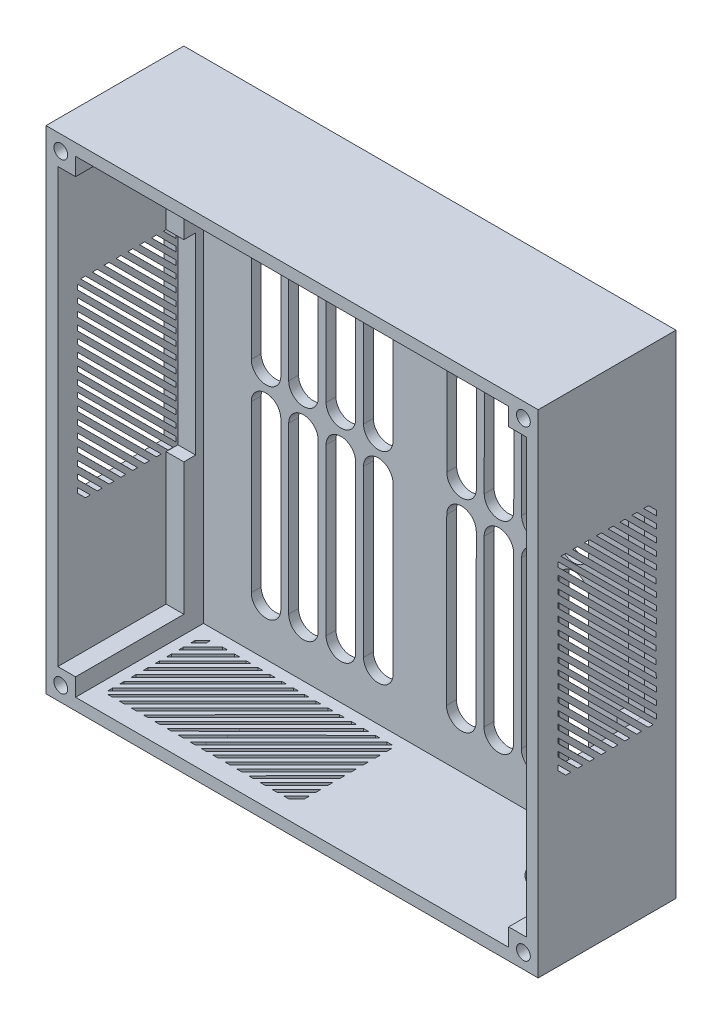
SolidWorks part; units mm, degrees
ref_plane "Plano frontal" through (0, 0, 0) normal (0, 0, 1) x (1, 0, 0)
ref_plane "Plano superior" through (0, 0, 0) normal (0, 1, 0) x (1, 0, 0)
ref_plane "Plano direito" through (0, 0, 0) normal (1, 0, 0) x (0, 0, -1)
sketch "Esboço1" plane through (0, 0, 0) normal (0, 0, 1) x (1, 0, 0)
  line L1 (-16.5696, 239.8339) -> (233.4304, 239.8339)
  line L2 (-16.5696, 239.8339) -> (-16.5696, -10.1661)
  line L3 (-16.5696, -10.1661) -> (233.4304, -10.1661)
  line L4 (233.4304, 239.8339) -> (233.4304, -10.1661)
  dimension "D1" = 250
  dimension "D2" = 250
extrude "Ressalto-extrusão1" add sketch "Esboço1" along normal blind 70 contours L2 L1 L4 L3
sketch "Esboço2" plane through (0, 0, 70) normal (0, 0, 1) x (1, 0, 0)
  line L0 (233.4304, 239.8339) -> (233.4304, -10.1661) construction
  line L1 (-10.5696, 233.8339) -> (227.4304, 233.8339)
  line L2 (-10.5696, 233.8339) -> (-10.5696, -4.1661)
  line L3 (-10.5696, -4.1661) -> (227.4304, -4.1661)
  line L4 (227.4304, 233.8339) -> (227.4304, -4.1661)
  line L5 (-16.5696, 239.8339) -> (233.4304, 239.8339) construction
  line L6 (-16.5696, 239.8339) -> (-16.5696, -10.1661) construction
  line L7 (-16.5696, -10.1661) -> (233.4304, -10.1661) construction
  dimension "D1" = 6
  dimension "D2" = 6
  dimension "D3" = 6
  dimension "D4" = 6
extrude "Corte-extrusão1" cut sketch "Esboço2" against normal blind 55
sketch "Esboço3" plane through (0, 0, 15) normal (0, 0, 1) x (1, 0, 0)
  line L0 (16.5131, 123.2364) -> (114.7807, 123.244)
  line L1 (16.3207, 123.1057) -> (16.3131, 223.614)
  line L2 (16.3748, 223.7141) -> (114.8731, 223.7141)
  line L3 (114.7807, 123.244) -> (114.7731, 223.5216)
  line L4 (215.3156, 223.7537) -> (117.0479, 223.7536)
  line L5 (215.5079, 223.8844) -> (215.5079, 123.3761)
  line L6 (117.0479, 123.4759) -> (215.5079, 123.3761)
  line L7 (117.0479, 223.7536) -> (117.0479, 123.4759)
  line L10 (16.567, 20.9373) -> (114.8346, 20.9449)
  line L11 (16.3746, 20.8067) -> (16.367, 121.3149)
  line L12 (16.4288, 121.4073) -> (99.2081, 121.4137)
  line L13 (114.8346, 20.9449) -> (114.827, 121.2225)
  line L14 (215.3478, 121.4314) -> (117.0801, 121.4238)
  line L15 (215.5401, 121.5621) -> (215.5477, 21.0538)
  line L16 (215.486, 20.9614) -> (116.9877, 20.9538)
  line L17 (117.0801, 121.4238) -> (117.0877, 21.1462)
  line L21 (-16.5696, -10.1661) -> (233.4304, -10.1661) construction
  line L23 (114.7807, 123.244) -> (117.0801, 121.4238) construction
  line L24 (99.2081, 121.4137) -> (114.827, 121.2225)
  line L25 (-16.5696, 239.8339) -> (233.4304, -10.1661) construction
  line L26 (-16.5696, -10.1661) -> (233.4304, 239.8339) construction
  arc A0 (59.4431, 138.154) -> (59.4431, 125.154) centre (59.4431, 131.654) ccw
  arc A1 (59.4431, 125.154) -> (59.4431, 138.154) centre (59.4431, 131.654) ccw
  arc A2 (40.4431, 138.154) -> (40.4431, 125.154) centre (40.4431, 131.654) ccw
  arc A3 (40.4431, 125.154) -> (40.4431, 138.154) centre (40.4431, 131.654) ccw
  arc A4 (40.4431, 152.154) -> (40.4431, 139.154) centre (40.4431, 145.654) ccw
  arc A5 (40.4431, 139.154) -> (40.4431, 152.154) centre (40.4431, 145.654) ccw
  arc A6 (59.4431, 152.154) -> (59.4431, 139.154) centre (59.4431, 145.654) ccw
  arc A7 (59.4431, 139.154) -> (59.4431, 152.154) centre (59.4431, 145.654) ccw
  arc A8 (78.4431, 152.154) -> (78.4431, 139.154) centre (78.4431, 145.654) ccw
  arc A9 (78.4431, 139.154) -> (78.4431, 152.154) centre (78.4431, 145.654) ccw
  arc A10 (78.4431, 138.154) -> (78.4431, 125.154) centre (78.4431, 131.654) ccw
  arc A11 (78.4431, 125.154) -> (78.4431, 138.154) centre (78.4431, 131.654) ccw
  arc A12 (97.4431, 138.154) -> (97.4431, 125.154) centre (97.4431, 131.654) ccw
  arc A13 (97.4431, 125.154) -> (97.4431, 138.154) centre (97.4431, 131.654) ccw
  arc A14 (97.4431, 152.154) -> (97.4431, 139.154) centre (97.4431, 145.654) ccw
  arc A15 (97.4431, 139.154) -> (97.4431, 152.154) centre (97.4431, 145.654) ccw
  arc A16 (97.4431, 166.154) -> (97.4431, 153.154) centre (97.4431, 159.654) ccw
  arc A17 (97.4431, 153.154) -> (97.4431, 166.154) centre (97.4431, 159.654) ccw
  arc A18 (78.4431, 166.154) -> (78.4431, 153.154) centre (78.4431, 159.654) ccw
  arc A19 (78.4431, 153.154) -> (78.4431, 166.154) centre (78.4431, 159.654) ccw
  arc A20 (59.4431, 166.154) -> (59.4431, 153.154) centre (59.4431, 159.654) ccw
  arc A21 (59.4431, 153.154) -> (59.4431, 166.154) centre (59.4431, 159.654) ccw
  arc A22 (40.4431, 166.154) -> (40.4431, 153.154) centre (40.4431, 159.654) ccw
  arc A23 (40.4431, 153.154) -> (40.4431, 166.154) centre (40.4431, 159.654) ccw
  arc A24 (40.4431, 180.154) -> (40.4431, 167.154) centre (40.4431, 173.654) ccw
  arc A25 (40.4431, 167.154) -> (40.4431, 180.154) centre (40.4431, 173.654) ccw
  arc A26 (59.4431, 180.154) -> (59.4431, 167.154) centre (59.4431, 173.654) ccw
  arc A27 (59.4431, 167.154) -> (59.4431, 180.154) centre (59.4431, 173.654) ccw
  arc A28 (78.4431, 180.154) -> (78.4431, 167.154) centre (78.4431, 173.654) ccw
  arc A29 (78.4431, 167.154) -> (78.4431, 180.154) centre (78.4431, 173.654) ccw
  arc A30 (97.4431, 180.154) -> (97.4431, 167.154) centre (97.4431, 173.654) ccw
  arc A31 (97.4431, 167.154) -> (97.4431, 180.154) centre (97.4431, 173.654) ccw
  arc A32 (97.4431, 194.154) -> (97.4431, 181.154) centre (97.4431, 187.654) ccw
  arc A33 (97.4431, 181.154) -> (97.4431, 194.154) centre (97.4431, 187.654) ccw
  arc A34 (78.4431, 194.154) -> (78.4431, 181.154) centre (78.4431, 187.654) ccw
  arc A35 (78.4431, 181.154) -> (78.4431, 194.154) centre (78.4431, 187.654) ccw
  arc A36 (59.4431, 194.154) -> (59.4431, 181.154) centre (59.4431, 187.654) ccw
  arc A37 (59.4431, 181.154) -> (59.4431, 194.154) centre (59.4431, 187.654) ccw
  arc A38 (40.4431, 194.154) -> (40.4431, 181.154) centre (40.4431, 187.654) ccw
  arc A39 (40.4431, 181.154) -> (40.4431, 194.154) centre (40.4431, 187.654) ccw
  arc A40 (40.4431, 208.154) -> (40.4431, 195.154) centre (40.4431, 201.654) ccw
  arc A41 (40.4431, 195.154) -> (40.4431, 208.154) centre (40.4431, 201.654) ccw
  arc A42 (59.4431, 208.154) -> (59.4431, 195.154) centre (59.4431, 201.654) ccw
  arc A43 (59.4431, 195.154) -> (59.4431, 208.154) centre (59.4431, 201.654) ccw
  arc A44 (78.4431, 208.154) -> (78.4431, 195.154) centre (78.4431, 201.654) ccw
  arc A45 (78.4431, 195.154) -> (78.4431, 208.154) centre (78.4431, 201.654) ccw
  arc A46 (97.4431, 208.154) -> (97.4431, 195.154) centre (97.4431, 201.654) ccw
  arc A47 (97.4431, 195.154) -> (97.4431, 208.154) centre (97.4431, 201.654) ccw
  arc A48 (97.4431, 222.154) -> (97.4431, 209.154) centre (97.4431, 215.654) ccw
  arc A49 (97.4431, 209.154) -> (97.4431, 222.154) centre (97.4431, 215.654) ccw
  arc A50 (78.4431, 222.154) -> (78.4431, 209.154) centre (78.4431, 215.654) ccw
  arc A51 (78.4431, 209.154) -> (78.4431, 222.154) centre (78.4431, 215.654) ccw
  arc A52 (59.4431, 222.154) -> (59.4431, 209.154) centre (59.4431, 215.654) ccw
  arc A53 (59.4431, 209.154) -> (59.4431, 222.154) centre (59.4431, 215.654) ccw
  arc A54 (40.4431, 222.154) -> (40.4431, 209.154) centre (40.4431, 215.654) ccw
  arc A55 (40.4431, 209.154) -> (40.4431, 222.154) centre (40.4431, 215.654) ccw
  circle A56 centre (20.8131, 210.774) radius 0.975
  circle A57 centre (20.9431, 217.524) radius 0.975
  circle A58 centre (110.4831, 207.064) radius 0.975
  circle A59 centre (110.4831, 213.114) radius 0.975
  circle A60 centre (110.6631, 136.644) radius 0.975
  circle A61 centre (110.6031, 142.634) radius 0.975
  circle A62 centre (20.6431, 132.314) radius 0.975
  circle A63 centre (20.6431, 138.364) radius 0.975
  arc A64 (172.3779, 208.8361) -> (172.3779, 221.8361) centre (172.3779, 215.3361) ccw
  arc A65 (172.3779, 221.8361) -> (172.3779, 208.8361) centre (172.3779, 215.3361) ccw
  arc A66 (191.3779, 208.8361) -> (191.3779, 221.8361) centre (191.3779, 215.3361) ccw
  arc A67 (191.3779, 221.8361) -> (191.3779, 208.8361) centre (191.3779, 215.3361) ccw
  arc A68 (191.3779, 194.8361) -> (191.3779, 207.8361) centre (191.3779, 201.3361) ccw
  arc A69 (191.3779, 207.8361) -> (191.3779, 194.8361) centre (191.3779, 201.3361) ccw
  arc A70 (172.3779, 194.8361) -> (172.3779, 207.8361) centre (172.3779, 201.3361) ccw
  arc A71 (172.3779, 207.8361) -> (172.3779, 194.8361) centre (172.3779, 201.3361) ccw
  arc A72 (153.3779, 194.8361) -> (153.3779, 207.8361) centre (153.3779, 201.3361) ccw
  arc A73 (153.3779, 207.8361) -> (153.3779, 194.8361) centre (153.3779, 201.3361) ccw
  arc A74 (153.3779, 208.8361) -> (153.3779, 221.8361) centre (153.3779, 215.3361) ccw
  arc A75 (153.3779, 221.8361) -> (153.3779, 208.8361) centre (153.3779, 215.3361) ccw
  arc A76 (134.3779, 208.8361) -> (134.3779, 221.8361) centre (134.3779, 215.3361) ccw
  arc A77 (134.3779, 221.8361) -> (134.3779, 208.8361) centre (134.3779, 215.3361) ccw
  arc A78 (134.3779, 194.8361) -> (134.3779, 207.8361) centre (134.3779, 201.3361) ccw
  arc A79 (134.3779, 207.8361) -> (134.3779, 194.8361) centre (134.3779, 201.3361) ccw
  arc A80 (134.3779, 180.8361) -> (134.3779, 193.8361) centre (134.3779, 187.3361) ccw
  arc A81 (134.3779, 193.8361) -> (134.3779, 180.8361) centre (134.3779, 187.3361) ccw
  arc A82 (153.3779, 180.8361) -> (153.3779, 193.8361) centre (153.3779, 187.3361) ccw
  arc A83 (153.3779, 193.8361) -> (153.3779, 180.8361) centre (153.3779, 187.3361) ccw
  arc A84 (172.3779, 180.8361) -> (172.3779, 193.8361) centre (172.3779, 187.3361) ccw
  arc A85 (172.3779, 193.8361) -> (172.3779, 180.8361) centre (172.3779, 187.3361) ccw
  arc A86 (191.3779, 180.8361) -> (191.3779, 193.8361) centre (191.3779, 187.3361) ccw
  arc A87 (191.3779, 193.8361) -> (191.3779, 180.8361) centre (191.3779, 187.3361) ccw
  arc A88 (191.3779, 166.8361) -> (191.3779, 179.8361) centre (191.3779, 173.3361) ccw
  arc A89 (191.3779, 179.8361) -> (191.3779, 166.8361) centre (191.3779, 173.3361) ccw
  arc A90 (172.3779, 166.8361) -> (172.3779, 179.8361) centre (172.3779, 173.3361) ccw
  arc A91 (172.3779, 179.8361) -> (172.3779, 166.8361) centre (172.3779, 173.3361) ccw
  arc A92 (153.3779, 166.8361) -> (153.3779, 179.8361) centre (153.3779, 173.3361) ccw
  arc A93 (153.3779, 179.8361) -> (153.3779, 166.8361) centre (153.3779, 173.3361) ccw
  arc A94 (134.3779, 166.8361) -> (134.3779, 179.8361) centre (134.3779, 173.3361) ccw
  arc A95 (134.3779, 179.8361) -> (134.3779, 166.8361) centre (134.3779, 173.3361) ccw
  arc A96 (134.3779, 152.8361) -> (134.3779, 165.8361) centre (134.3779, 159.3361) ccw
  arc A97 (134.3779, 165.8361) -> (134.3779, 152.8361) centre (134.3779, 159.3361) ccw
  arc A98 (153.3779, 152.8361) -> (153.3779, 165.8361) centre (153.3779, 159.3361) ccw
  arc A99 (153.3779, 165.8361) -> (153.3779, 152.8361) centre (153.3779, 159.3361) ccw
  arc A100 (172.3779, 152.8361) -> (172.3779, 165.8361) centre (172.3779, 159.3361) ccw
  arc A101 (172.3779, 165.8361) -> (172.3779, 152.8361) centre (172.3779, 159.3361) ccw
  arc A102 (191.3779, 152.8361) -> (191.3779, 165.8361) centre (191.3779, 159.3361) ccw
  arc A103 (191.3779, 165.8361) -> (191.3779, 152.8361) centre (191.3779, 159.3361) ccw
  arc A104 (191.3779, 138.8361) -> (191.3779, 151.8361) centre (191.3779, 145.3361) ccw
  arc A105 (191.3779, 151.8361) -> (191.3779, 138.8361) centre (191.3779, 145.3361) ccw
  arc A106 (172.3779, 138.8361) -> (172.3779, 151.8361) centre (172.3779, 145.3361) ccw
  arc A107 (172.3779, 151.8361) -> (172.3779, 138.8361) centre (172.3779, 145.3361) ccw
  arc A108 (153.3779, 138.8361) -> (153.3779, 151.8361) centre (153.3779, 145.3361) ccw
  arc A109 (153.3779, 151.8361) -> (153.3779, 138.8361) centre (153.3779, 145.3361) ccw
  arc A110 (134.3779, 138.8361) -> (134.3779, 151.8361) centre (134.3779, 145.3361) ccw
  arc A111 (134.3779, 151.8361) -> (134.3779, 138.8361) centre (134.3779, 145.3361) ccw
  arc A112 (134.3779, 124.8361) -> (134.3779, 137.8361) centre (134.3779, 131.3361) ccw
  arc A113 (134.3779, 137.8361) -> (134.3779, 124.8361) centre (134.3779, 131.3361) ccw
  arc A114 (153.3779, 124.8361) -> (153.3779, 137.8361) centre (153.3779, 131.3361) ccw
  arc A115 (153.3779, 137.8361) -> (153.3779, 124.8361) centre (153.3779, 131.3361) ccw
  arc A116 (172.3779, 124.8361) -> (172.3779, 137.8361) centre (172.3779, 131.3361) ccw
  arc A117 (172.3779, 137.8361) -> (172.3779, 124.8361) centre (172.3779, 131.3361) ccw
  arc A118 (191.3779, 124.8361) -> (191.3779, 137.8361) centre (191.3779, 131.3361) ccw
  arc A119 (191.3779, 137.8361) -> (191.3779, 124.8361) centre (191.3779, 131.3361) ccw
  circle A120 centre (211.0079, 136.2161) radius 0.975
  circle A121 centre (210.8779, 129.4661) radius 0.975
  circle A122 centre (121.3379, 139.9261) radius 0.975
  circle A123 centre (121.3379, 133.8761) radius 0.975
  circle A124 centre (121.1579, 210.3461) radius 0.975
  circle A125 centre (121.2179, 204.3561) radius 0.975
  circle A126 centre (211.1779, 214.6761) radius 0.975
  circle A127 centre (211.1779, 208.6261) radius 0.975
  arc A128 (59.497, 35.8549) -> (59.497, 22.8549) centre (59.497, 29.3549) ccw
  arc A129 (59.497, 22.8549) -> (59.497, 35.8549) centre (59.497, 29.3549) ccw
  arc A130 (40.497, 35.8549) -> (40.497, 22.8549) centre (40.497, 29.3549) ccw
  arc A131 (40.497, 22.8549) -> (40.497, 35.8549) centre (40.497, 29.3549) ccw
  arc A132 (40.497, 49.8549) -> (40.497, 36.8549) centre (40.497, 43.3549) ccw
  arc A133 (40.497, 36.8549) -> (40.497, 49.8549) centre (40.497, 43.3549) ccw
  arc A134 (59.497, 49.8549) -> (59.497, 36.8549) centre (59.497, 43.3549) ccw
  arc A135 (59.497, 36.8549) -> (59.497, 49.8549) centre (59.497, 43.3549) ccw
  arc A136 (78.497, 49.8549) -> (78.497, 36.8549) centre (78.497, 43.3549) ccw
  arc A137 (78.497, 36.8549) -> (78.497, 49.8549) centre (78.497, 43.3549) ccw
  arc A138 (78.497, 35.8549) -> (78.497, 22.8549) centre (78.497, 29.3549) ccw
  arc A139 (78.497, 22.8549) -> (78.497, 35.8549) centre (78.497, 29.3549) ccw
  arc A140 (97.497, 35.8549) -> (97.497, 22.8549) centre (97.497, 29.3549) ccw
  arc A141 (97.497, 22.8549) -> (97.497, 35.8549) centre (97.497, 29.3549) ccw
  arc A142 (97.497, 49.8549) -> (97.497, 36.8549) centre (97.497, 43.3549) ccw
  arc A143 (97.497, 36.8549) -> (97.497, 49.8549) centre (97.497, 43.3549) ccw
  arc A144 (97.497, 63.8549) -> (97.497, 50.8549) centre (97.497, 57.3549) ccw
  arc A145 (97.497, 50.8549) -> (97.497, 63.8549) centre (97.497, 57.3549) ccw
  arc A146 (78.497, 63.8549) -> (78.497, 50.8549) centre (78.497, 57.3549) ccw
  arc A147 (78.497, 50.8549) -> (78.497, 63.8549) centre (78.497, 57.3549) ccw
  arc A148 (59.497, 63.8549) -> (59.497, 50.8549) centre (59.497, 57.3549) ccw
  arc A149 (59.497, 50.8549) -> (59.497, 63.8549) centre (59.497, 57.3549) ccw
  arc A150 (40.497, 63.8549) -> (40.497, 50.8549) centre (40.497, 57.3549) ccw
  arc A151 (40.497, 50.8549) -> (40.497, 63.8549) centre (40.497, 57.3549) ccw
  arc A152 (40.497, 77.8549) -> (40.497, 64.8549) centre (40.497, 71.3549) ccw
  arc A153 (40.497, 64.8549) -> (40.497, 77.8549) centre (40.497, 71.3549) ccw
  arc A154 (59.497, 77.8549) -> (59.497, 64.8549) centre (59.497, 71.3549) ccw
  arc A155 (59.497, 64.8549) -> (59.497, 77.8549) centre (59.497, 71.3549) ccw
  arc A156 (78.497, 77.8549) -> (78.497, 64.8549) centre (78.497, 71.3549) ccw
  arc A157 (78.497, 64.8549) -> (78.497, 77.8549) centre (78.497, 71.3549) ccw
  arc A158 (97.497, 77.8549) -> (97.497, 64.8549) centre (97.497, 71.3549) ccw
  arc A159 (97.497, 64.8549) -> (97.497, 77.8549) centre (97.497, 71.3549) ccw
  arc A160 (97.497, 91.8549) -> (97.497, 78.8549) centre (97.497, 85.3549) ccw
  arc A161 (97.497, 78.8549) -> (97.497, 91.8549) centre (97.497, 85.3549) ccw
  arc A162 (78.497, 91.8549) -> (78.497, 78.8549) centre (78.497, 85.3549) ccw
  arc A163 (78.497, 78.8549) -> (78.497, 91.8549) centre (78.497, 85.3549) ccw
  arc A164 (59.497, 91.8549) -> (59.497, 78.8549) centre (59.497, 85.3549) ccw
  arc A165 (59.497, 78.8549) -> (59.497, 91.8549) centre (59.497, 85.3549) ccw
  arc A166 (40.497, 91.8549) -> (40.497, 78.8549) centre (40.497, 85.3549) ccw
  arc A167 (40.497, 78.8549) -> (40.497, 91.8549) centre (40.497, 85.3549) ccw
  arc A168 (40.497, 105.8549) -> (40.497, 92.8549) centre (40.497, 99.3549) ccw
  arc A169 (40.497, 92.8549) -> (40.497, 105.8549) centre (40.497, 99.3549) ccw
  arc A170 (59.497, 105.8549) -> (59.497, 92.8549) centre (59.497, 99.3549) ccw
  arc A171 (59.497, 92.8549) -> (59.497, 105.8549) centre (59.497, 99.3549) ccw
  arc A172 (78.497, 105.8549) -> (78.497, 92.8549) centre (78.497, 99.3549) ccw
  arc A173 (78.497, 92.8549) -> (78.497, 105.8549) centre (78.497, 99.3549) ccw
  arc A174 (97.497, 105.8549) -> (97.497, 92.8549) centre (97.497, 99.3549) ccw
  arc A175 (97.497, 92.8549) -> (97.497, 105.8549) centre (97.497, 99.3549) ccw
  arc A176 (97.497, 119.8549) -> (97.497, 106.8549) centre (97.497, 113.3549) ccw
  arc A177 (97.497, 106.8549) -> (97.497, 119.8549) centre (97.497, 113.3549) ccw
  arc A178 (78.497, 119.8549) -> (78.497, 106.8549) centre (78.497, 113.3549) ccw
  arc A179 (78.497, 106.8549) -> (78.497, 119.8549) centre (78.497, 113.3549) ccw
  arc A180 (59.497, 119.8549) -> (59.497, 106.8549) centre (59.497, 113.3549) ccw
  arc A181 (59.497, 106.8549) -> (59.497, 119.8549) centre (59.497, 113.3549) ccw
  arc A182 (40.497, 119.8549) -> (40.497, 106.8549) centre (40.497, 113.3549) ccw
  arc A183 (40.497, 106.8549) -> (40.497, 119.8549) centre (40.497, 113.3549) ccw
  circle A184 centre (20.867, 108.4749) radius 0.975
  circle A185 centre (20.997, 115.2249) radius 0.975
  circle A186 centre (110.537, 104.7649) radius 0.975
  circle A187 centre (110.537, 110.8149) radius 0.975
  circle A188 centre (110.717, 34.3449) radius 0.975
  circle A189 centre (110.657, 40.3349) radius 0.975
  circle A190 centre (20.697, 30.0149) radius 0.975
  circle A191 centre (20.697, 36.0649) radius 0.975
  arc A192 (172.4177, 106.5138) -> (172.4177, 119.5138) centre (172.4177, 113.0138) ccw
  arc A193 (172.4177, 119.5138) -> (172.4177, 106.5138) centre (172.4177, 113.0138) ccw
  arc A194 (191.4177, 106.5138) -> (191.4177, 119.5138) centre (191.4177, 113.0138) ccw
  arc A195 (191.4177, 119.5138) -> (191.4177, 106.5138) centre (191.4177, 113.0138) ccw
  arc A196 (191.4177, 92.5138) -> (191.4177, 105.5138) centre (191.4177, 99.0138) ccw
  arc A197 (191.4177, 105.5138) -> (191.4177, 92.5138) centre (191.4177, 99.0138) ccw
  arc A198 (172.4177, 92.5138) -> (172.4177, 105.5138) centre (172.4177, 99.0138) ccw
  arc A199 (172.4177, 105.5138) -> (172.4177, 92.5138) centre (172.4177, 99.0138) ccw
  arc A200 (153.4177, 92.5138) -> (153.4177, 105.5138) centre (153.4177, 99.0138) ccw
  arc A201 (153.4177, 105.5138) -> (153.4177, 92.5138) centre (153.4177, 99.0138) ccw
  arc A202 (153.4177, 106.5138) -> (153.4177, 119.5138) centre (153.4177, 113.0138) ccw
  arc A203 (153.4177, 119.5138) -> (153.4177, 106.5138) centre (153.4177, 113.0138) ccw
  arc A204 (134.4177, 106.5138) -> (134.4177, 119.5138) centre (134.4177, 113.0138) ccw
  arc A205 (134.4177, 119.5138) -> (134.4177, 106.5138) centre (134.4177, 113.0138) ccw
  arc A206 (134.4177, 92.5138) -> (134.4177, 105.5138) centre (134.4177, 99.0138) ccw
  arc A207 (134.4177, 105.5138) -> (134.4177, 92.5138) centre (134.4177, 99.0138) ccw
  arc A208 (134.4177, 78.5138) -> (134.4177, 91.5138) centre (134.4177, 85.0138) ccw
  arc A209 (134.4177, 91.5138) -> (134.4177, 78.5138) centre (134.4177, 85.0138) ccw
  arc A210 (153.4177, 78.5138) -> (153.4177, 91.5138) centre (153.4177, 85.0138) ccw
  arc A211 (153.4177, 91.5138) -> (153.4177, 78.5138) centre (153.4177, 85.0138) ccw
  arc A212 (172.4177, 78.5138) -> (172.4177, 91.5138) centre (172.4177, 85.0138) ccw
  arc A213 (172.4177, 91.5138) -> (172.4177, 78.5138) centre (172.4177, 85.0138) ccw
  arc A214 (191.4177, 78.5138) -> (191.4177, 91.5138) centre (191.4177, 85.0138) ccw
  arc A215 (191.4177, 91.5138) -> (191.4177, 78.5138) centre (191.4177, 85.0138) ccw
  arc A216 (191.4177, 64.5138) -> (191.4177, 77.5138) centre (191.4177, 71.0138) ccw
  arc A217 (191.4177, 77.5138) -> (191.4177, 64.5138) centre (191.4177, 71.0138) ccw
  arc A218 (172.4177, 64.5138) -> (172.4177, 77.5138) centre (172.4177, 71.0138) ccw
  arc A219 (172.4177, 77.5138) -> (172.4177, 64.5138) centre (172.4177, 71.0138) ccw
  arc A220 (153.4177, 64.5138) -> (153.4177, 77.5138) centre (153.4177, 71.0138) ccw
  arc A221 (153.4177, 77.5138) -> (153.4177, 64.5138) centre (153.4177, 71.0138) ccw
  arc A222 (134.4177, 64.5138) -> (134.4177, 77.5138) centre (134.4177, 71.0138) ccw
  arc A223 (134.4177, 77.5138) -> (134.4177, 64.5138) centre (134.4177, 71.0138) ccw
  arc A224 (134.4177, 50.5138) -> (134.4177, 63.5138) centre (134.4177, 57.0138) ccw
  arc A225 (134.4177, 63.5138) -> (134.4177, 50.5138) centre (134.4177, 57.0138) ccw
  arc A226 (153.4177, 50.5138) -> (153.4177, 63.5138) centre (153.4177, 57.0138) ccw
  arc A227 (153.4177, 63.5138) -> (153.4177, 50.5138) centre (153.4177, 57.0138) ccw
  arc A228 (172.4177, 50.5138) -> (172.4177, 63.5138) centre (172.4177, 57.0138) ccw
  arc A229 (172.4177, 63.5138) -> (172.4177, 50.5138) centre (172.4177, 57.0138) ccw
  arc A230 (191.4177, 50.5138) -> (191.4177, 63.5138) centre (191.4177, 57.0138) ccw
  arc A231 (191.4177, 63.5138) -> (191.4177, 50.5138) centre (191.4177, 57.0138) ccw
  arc A232 (191.4177, 36.5138) -> (191.4177, 49.5138) centre (191.4177, 43.0138) ccw
  arc A233 (191.4177, 49.5138) -> (191.4177, 36.5138) centre (191.4177, 43.0138) ccw
  arc A234 (172.4177, 36.5138) -> (172.4177, 49.5138) centre (172.4177, 43.0138) ccw
  arc A235 (172.4177, 49.5138) -> (172.4177, 36.5138) centre (172.4177, 43.0138) ccw
  arc A236 (153.4177, 36.5138) -> (153.4177, 49.5138) centre (153.4177, 43.0138) ccw
  arc A237 (153.4177, 49.5138) -> (153.4177, 36.5138) centre (153.4177, 43.0138) ccw
  arc A238 (134.4177, 36.5138) -> (134.4177, 49.5138) centre (134.4177, 43.0138) ccw
  arc A239 (134.4177, 49.5138) -> (134.4177, 36.5138) centre (134.4177, 43.0138) ccw
  arc A240 (134.4177, 22.5138) -> (134.4177, 35.5138) centre (134.4177, 29.0138) ccw
  arc A241 (134.4177, 35.5138) -> (134.4177, 22.5138) centre (134.4177, 29.0138) ccw
  arc A242 (153.4177, 22.5138) -> (153.4177, 35.5138) centre (153.4177, 29.0138) ccw
  arc A243 (153.4177, 35.5138) -> (153.4177, 22.5138) centre (153.4177, 29.0138) ccw
  arc A244 (172.4177, 22.5138) -> (172.4177, 35.5138) centre (172.4177, 29.0138) ccw
  arc A245 (172.4177, 35.5138) -> (172.4177, 22.5138) centre (172.4177, 29.0138) ccw
  arc A246 (191.4177, 22.5138) -> (191.4177, 35.5138) centre (191.4177, 29.0138) ccw
  arc A247 (191.4177, 35.5138) -> (191.4177, 22.5138) centre (191.4177, 29.0138) ccw
  circle A248 centre (211.0477, 33.8938) radius 0.975
  circle A249 centre (210.9177, 27.1438) radius 0.975
  circle A250 centre (121.3777, 37.6038) radius 0.975
  circle A251 centre (121.3777, 31.5538) radius 0.975
  circle A252 centre (121.1977, 108.0238) radius 0.975
  circle A253 centre (121.2577, 102.0338) radius 0.975
  circle A254 centre (211.2177, 112.3538) radius 0.975
  circle A255 centre (211.2177, 106.3038) radius 0.975
  point P135 (166.2214, 173.6225)
  point P406 (166.2574, 71.2965)
  point P544 (115.9304, 122.3339)
  point P546 (115.9304, 122.3339)
sketch "Esboço5" plane through (0, 239.8339, 0) normal (0, 1, 0) x (1, 0, 0)
  line L0 (39.532, 0) -> (39.532, -40.1721)
  line L1 (-16.5696, 0) -> (233.4304, 0) construction
  line L2 (-48.9022, 48.2621) -> (39.532, -40.1721)
  line L3 (127.9662, 48.2621) -> (39.532, -40.1721)
  line L4 (-48.9022, 48.2621) -> (-150.6401, 150) construction
  line L5 (39.532, 0) -> (39.532, 150) construction
  line L6 (-150.6401, 150) -> (229.7041, 150) construction
  line L7 (127.9662, 48.2621) -> (375.3202, 295.6161) construction
  arc A0 (-48.9022, 48.2621) -> (127.9662, 48.2621) centre (39.532, -40.1721) cw
  dimension "D1" = 90
  dimension "D2" = 45
sketch "Esboço6" plane through (0, 0, 15) normal (0, 0, 1) x (1, 0, 0)
  line L0 (22.6955, 208.1676) -> (22.6955, 124.154)
  line L1 (37.6955, 208.1676) -> (37.6955, 124.154)
  line L2 (41.6955, 208.1676) -> (41.6955, 124.154)
  line L3 (56.6955, 124.154) -> (56.6955, 208.1676)
  line L4 (60.6955, 208.1676) -> (60.6955, 124.154)
  line L5 (79.6955, 208.1676) -> (79.6955, 124.154)
  line L6 (75.6955, 124.154) -> (75.6955, 208.1676)
  line L7 (94.6955, 124.154) -> (94.6955, 208.1676)
  line L9 (94.6955, 105.5138) -> (94.6955, 21.5002)
  line L17 (-10.5696, 114.8339) -> (227.4304, 114.8339) construction
  line L18 (-10.5696, 233.8339) -> (-10.5696, -4.1661) construction
  line L19 (227.4304, -4.1661) -> (227.4304, 233.8339) construction
  line L20 (75.6955, 105.5138) -> (75.6955, 21.5002)
  line L21 (79.6955, 21.5002) -> (79.6955, 105.5138)
  line L22 (60.6955, 21.5002) -> (60.6955, 105.5138)
  line L23 (56.6955, 105.5138) -> (56.6955, 21.5002)
  line L24 (41.6955, 21.5002) -> (41.6955, 105.5138)
  line L25 (37.6955, 21.5002) -> (37.6955, 105.5138)
  line L26 (22.6955, 21.5002) -> (22.6955, 105.5138)
  line L27 (193.8751, 21.3832) -> (193.9899, 105.3967)
  line L28 (108.418, 215.6572) -> (108.4304, 233.8339) construction
  line L29 (227.4304, 233.8339) -> (-10.5696, 233.8339) construction
  line L30 (178.8751, 21.4037) -> (178.9899, 105.4172)
  line L31 (174.8751, 21.4092) -> (174.9899, 105.4227)
  line L32 (159.9899, 105.4432) -> (159.8751, 21.4297)
  line L33 (155.8751, 21.4351) -> (155.9899, 105.4487)
  line L34 (136.8752, 21.4611) -> (136.99, 105.4746)
  line L35 (140.99, 105.4692) -> (140.8752, 21.4556)
  line L36 (121.99, 105.4951) -> (121.8752, 21.4816)
  line L37 (122.0155, 124.1353) -> (122.1303, 208.1489)
  line L38 (141.0154, 124.1094) -> (141.1302, 208.1229)
  line L39 (137.1302, 208.1284) -> (137.0154, 124.1148)
  line L40 (156.1302, 208.1024) -> (156.0154, 124.0889)
  line L41 (160.0154, 124.0834) -> (160.1302, 208.0969)
  line L42 (175.1302, 208.0764) -> (175.0154, 124.0629)
  line L43 (179.1302, 208.071) -> (179.0154, 124.0574)
  line L44 (194.1302, 208.0505) -> (194.0154, 124.0369)
  line L45 (-10.5696, -4.1661) -> (227.4304, -4.1661) construction
  arc A112 (37.6955, 208.1676) -> (22.6955, 208.1676) centre (30.1955, 208.1676) ccw
  arc A113 (22.6955, 124.154) -> (37.6955, 124.154) centre (30.1955, 124.154) ccw
  arc A114 (41.6955, 208.1676) -> (56.6955, 208.1676) centre (49.1955, 208.1676) cw
  arc A115 (41.6955, 124.154) -> (56.6955, 124.154) centre (49.1955, 124.154) ccw
  arc A116 (60.6955, 208.1676) -> (75.6955, 208.1676) centre (68.1955, 208.1676) cw
  arc A117 (60.6955, 124.154) -> (75.6955, 124.154) centre (68.1955, 124.154) ccw
  arc A118 (79.6955, 208.1676) -> (94.6955, 208.1676) centre (87.1955, 208.1676) cw
  arc A119 (79.6955, 124.154) -> (94.6955, 124.154) centre (87.1955, 124.154) ccw
  arc A128 (79.6955, 105.5138) -> (94.6955, 105.5138) centre (87.1955, 105.5138) cw
  arc A129 (79.6955, 21.5002) -> (94.6955, 21.5002) centre (87.1955, 21.5002) ccw
  arc A130 (60.6955, 105.5138) -> (75.6955, 105.5138) centre (68.1955, 105.5138) cw
  arc A131 (60.6955, 21.5002) -> (75.6955, 21.5002) centre (68.1955, 21.5002) ccw
  arc A132 (41.6955, 105.5138) -> (56.6955, 105.5138) centre (49.1955, 105.5138) cw
  arc A133 (41.6955, 21.5002) -> (56.6955, 21.5002) centre (49.1955, 21.5002) ccw
  arc A134 (22.6955, 105.5138) -> (37.6955, 105.5138) centre (30.1955, 105.5138) cw
  arc A135 (37.6955, 21.5002) -> (22.6955, 21.5002) centre (30.1955, 21.5002) cw
  arc A136 (178.8751, 21.4037) -> (193.8751, 21.3832) centre (186.3751, 21.3935) ccw
  arc A137 (193.9899, 105.3967) -> (178.9899, 105.4172) centre (186.4899, 105.407) ccw
  arc A138 (174.8751, 21.4092) -> (159.8751, 21.4297) centre (167.3751, 21.4194) cw
  arc A139 (174.9899, 105.4227) -> (159.9899, 105.4432) centre (167.4899, 105.433) ccw
  arc A140 (155.8751, 21.4351) -> (140.8752, 21.4556) centre (148.3751, 21.4454) cw
  arc A141 (155.9899, 105.4487) -> (140.99, 105.4692) centre (148.49, 105.4589) ccw
  arc A142 (136.8752, 21.4611) -> (121.8752, 21.4816) centre (129.3752, 21.4713) cw
  arc A143 (136.99, 105.4746) -> (121.99, 105.4951) centre (129.49, 105.4849) ccw
  arc A144 (137.0154, 124.1148) -> (122.0155, 124.1353) centre (129.5154, 124.1251) cw
  arc A145 (137.1302, 208.1284) -> (122.1303, 208.1489) centre (129.6303, 208.1386) ccw
  arc A146 (156.0154, 124.0889) -> (141.0154, 124.1094) centre (148.5154, 124.0991) cw
  arc A147 (156.1302, 208.1024) -> (141.1302, 208.1229) centre (148.6302, 208.1127) ccw
  arc A148 (175.0154, 124.0629) -> (160.0154, 124.0834) centre (167.5154, 124.0731) cw
  arc A149 (175.1302, 208.0764) -> (160.1302, 208.0969) centre (167.6302, 208.0867) ccw
  arc A150 (194.0154, 124.0369) -> (179.0154, 124.0574) centre (186.5154, 124.0472) cw
  arc A151 (179.1302, 208.071) -> (194.1302, 208.0505) centre (186.6302, 208.0607) cw
  dimension "D1" = 19
  dimension "D2" = 19
  dimension "D3" = 19
  dimension "D4" = 19
  dimension "D14" = 7.5
  dimension "D15" = 7.5
  dimension "D16" = 7.5
  dimension "D17" = 7.5
  dimension "D5" = 19
  dimension "D6" = 19
  dimension "D7" = 19
  dimension "D8" = 19
  dimension "D9" = 18.9745
  dimension "D10" = 19
  dimension "D11" = 19
  dimension "D12" = 19
  dimension "D13" = 21.2174
extrude "Corte-extrusão2" cut sketch "Esboço6" against normal through all
sketch "Esboço7" plane through (0, 0, 15) normal (0, 0, 1) x (1, 0, 0)
  line L0 (-16.5696, 239.8339) -> (233.4304, -10.1661) construction
  line L1 (-1.5696, 224.8339) -> (218.4304, 224.8339)
  line L2 (-1.5696, 224.8339) -> (-1.5696, -4.1661)
  line L3 (-1.5696, -4.1661) -> (218.4304, -4.1661)
  line L4 (218.4304, 224.8339) -> (218.4304, -4.1661)
  line L5 (-16.5696, 239.8339) -> (-16.5696, -10.1661) construction
  line L8 (233.4304, 239.8339) -> (233.4304, -10.1661) construction
  line L9 (-10.5696, -4.1661) -> (227.4304, -4.1661) construction
  dimension "D1" = 15
  dimension "D2" = 0
  dimension "D3" = 15
extrude "Corte-extrusão3" cut sketch "Esboço7" against normal blind 10
sketch "Esboço8" plane through (-16.5696, 0, 0) normal (-1, 0, 0) x (0, 0, 1)
  line L0 (10, 119.6601) -> (60, 119.6601) construction
  line L7 (70, -10.1661) -> (0, -10.1661) construction
  line L8 (60, 72.098) -> (60, 169.619) construction
  line L9 (60, 169.619) -> (10, 169.619) construction
  line L10 (10, 169.619) -> (10, 72.098) construction
  line L11 (70, 239.8339) -> (70, -10.1661) construction
  line L12 (0, 239.8339) -> (0, -10.1661) construction
  line L13 (70, 239.8339) -> (0, 239.8339) construction
  line L14 (10, 165.6574) -> (13.9616, 169.619)
  line L15 (10, 163.1574) -> (16.4616, 169.619)
  line L16 (16.4616, 169.619) -> (13.9616, 169.619)
  line L17 (10, 163.1574) -> (10, 165.6574)
  line L18 (9.9567, 159.7022) -> (19.8621, 169.619)
  line L19 (9.9581, 157.2022) -> (22.4616, 169.619)
  line L20 (22.4616, 169.619) -> (19.8621, 169.619)
  line L21 (9.9581, 157.2022) -> (9.9567, 159.7022)
  line L22 (9.9663, 153.6875) -> (25.895, 169.619)
  line L23 (9.9666, 151.1875) -> (28.4616, 169.619)
  line L24 (28.4616, 169.619) -> (25.895, 169.619)
  line L25 (9.9666, 151.1875) -> (9.9663, 153.6875)
  line L26 (9.9685, 147.6916) -> (31.8987, 169.619)
  line L27 (9.9683, 145.1916) -> (34.4616, 169.619)
  line L28 (34.4616, 169.619) -> (31.8987, 169.619)
  line L29 (9.9683, 145.1916) -> (9.9685, 147.6916)
  line L30 (9.97, 141.6894) -> (37.9164, 169.619)
  line L31 (9.9692, 139.1894) -> (40.4616, 169.619)
  line L32 (40.4616, 169.619) -> (37.9164, 169.619)
  line L33 (9.9692, 139.1894) -> (9.97, 141.6894)
  line L34 (10.0431, 135.6576) -> (43.9616, 169.619)
  line L35 (10.0431, 133.1576) -> (46.5045, 169.619)
  line L36 (46.5045, 169.619) -> (43.9616, 169.619)
  line L37 (10.0431, 133.1576) -> (10.0431, 135.6576)
  line L38 (10.0003, 129.6577) -> (50.0083, 169.619)
  line L39 (10.0003, 127.1577) -> (52.5115, 169.619)
  line L40 (52.5115, 169.619) -> (50.0083, 169.619)
  line L41 (10.0003, 127.1577) -> (10.0003, 129.6577)
  line L42 (9.9759, 123.6892) -> (55.9616, 169.619)
  line L43 (9.9744, 121.1892) -> (58.4616, 169.619)
  line L44 (58.4616, 169.619) -> (55.9616, 169.619)
  line L45 (9.9744, 121.1892) -> (9.9759, 123.6892)
  line L52 (59.5407, 169.1421) -> (10, 119.6601) construction
  line L54 (60.0164, 168.0625) -> (60.0134, 165.5625)
  line L55 (11.5291, 119.6327) -> (60.0164, 168.0625)
  line L56 (14.0291, 119.6299) -> (60.0134, 165.5625)
  line L58 (60.0093, 162.1124) -> (60.0063, 159.6091)
  line L62 (60.0022, 156.1054) -> (59.9992, 153.5625)
  line L66 (59.995, 150.0625) -> (59.992, 147.5173)
  line L70 (59.9879, 144.0625) -> (59.9849, 141.4996)
  line L74 (59.9808, 138.0625) -> (59.9778, 135.4958)
  line L78 (59.9737, 132.0625) -> (59.9706, 129.4629)
  line L82 (59.9666, 126.0625) -> (59.9636, 123.5625)
  line L85 (58.4452, 122.0457) -> (59.9636, 123.5625)
  line L86 (55.9376, 122.0484) -> (59.9666, 126.0625)
  line L87 (57.5669, 119.6601) -> (10, 119.6601) construction
  line L88 (50.0305, 122.0548) -> (59.9737, 132.0625)
  line L93 (10.0431, 112.0466) -> (20.0637, 122.0871)
  line L94 (10.0404, 109.5466) -> (22.5563, 122.0844)
  line L96 (10.0404, 109.5466) -> (10.0431, 112.0466)
  line L97 (10.0366, 106.0447) -> (25.9566, 122.0808)
  line L98 (10.0339, 103.5447) -> (28.4953, 122.078)
  line L100 (10.0339, 103.5447) -> (10.0366, 106.0447)
  line L101 (10.0302, 100.0431) -> (31.9981, 122.0743)
  line L102 (10.0275, 97.5729) -> (34.536, 122.0715)
  line L104 (10.0275, 97.5729) -> (10.0302, 100.0431)
  line L105 (10.0237, 94.0419) -> (38.0036, 122.0678)
  line L106 (10.021, 91.5783) -> (40.5338, 122.0651)
  line L108 (10.021, 91.5783) -> (10.0237, 94.0419)
  line L109 (10.0172, 88.0464) -> (44.003, 122.0613)
  line L110 (10.0146, 85.5883) -> (46.5255, 122.0586)
  line L112 (10.0146, 85.5883) -> (10.0172, 88.0464)
  line L113 (10.0107, 82.0549) -> (50.0305, 122.0548)
  line L114 (10.0081, 79.5986) -> (52.5452, 122.0521)
  line L116 (10.0081, 79.5986) -> (10.0107, 82.0549)
  line L117 (10.0013, 76.0898) -> (55.9376, 122.0484)
  line L118 (10.0017, 73.6544) -> (58.4452, 122.0457)
  line L120 (10.0017, 73.6544) -> (10.0013, 76.0898)
  line L121 (57.1391, 119.1863) -> (10, 72.098) construction
  line L122 (11.5565, 72.098) -> (13.9919, 72.095)
  line L123 (60, 120.4893) -> (60, 117.9817)
  line L124 (11.5565, 72.098) -> (60, 120.4893)
  line L125 (13.9919, 72.095) -> (60, 117.9817)
  line L126 (17.5006, 72.098) -> (19.957, 72.098)
  line L127 (60, 114.5892) -> (60, 112.0746)
  line L128 (17.5006, 72.098) -> (60, 114.5892)
  line L129 (19.957, 72.098) -> (60, 112.0746)
  line L130 (23.4903, 72.098) -> (25.9484, 72.098)
  line L131 (60, 108.5696) -> (60, 106.0471)
  line L132 (23.4903, 72.098) -> (60, 108.5696)
  line L133 (25.9484, 72.098) -> (60, 106.0471)
  line L134 (29.4803, 72.098) -> (31.9439, 72.098)
  line L135 (60, 102.5778) -> (60, 100.0476)
  line L136 (29.4803, 72.098) -> (60, 102.5778)
  line L137 (31.9439, 72.098) -> (60, 100.0476)
  line L138 (35.475, 72.098) -> (37.9451, 72.098)
  line L139 (60, 96.58) -> (60, 94.0421)
  line L140 (35.475, 72.098) -> (60, 96.58)
  line L141 (37.9451, 72.098) -> (60, 94.0421)
  line L142 (41.4468, 72.098) -> (43.9468, 72.098)
  line L143 (60, 90.5394) -> (60, 88.0007)
  line L144 (41.4468, 72.098) -> (60, 90.5394)
  line L145 (43.9468, 72.098) -> (60, 88.0007)
  line L146 (47.4487, 72.098) -> (49.9487, 72.098)
  line L147 (60, 84.6003) -> (60, 82.1077)
  line L148 (47.4487, 72.098) -> (60, 84.6003)
  line L149 (49.9487, 72.098) -> (60, 82.1077)
  line L150 (53.4916, 72.098) -> (55.9916, 72.098)
  line L151 (60.0104, 78.5898) -> (60, 76.0898)
  line L152 (53.4916, 72.098) -> (60.0104, 78.5898)
  line L153 (55.9916, 72.098) -> (60, 76.0898)
  line L154 (11.5291, 119.6327) -> (10, 118.1054)
  line L155 (10, 118.1054) -> (10, 115.6054)
  line L156 (10, 115.6054) -> (14.0291, 119.6299)
  line L157 (20.0637, 122.0871) -> (60.0093, 162.1124)
  line L158 (22.5563, 122.0844) -> (60.0063, 159.6091)
  line L159 (25.9566, 122.0808) -> (60.0022, 156.1054)
  line L160 (28.4953, 122.078) -> (59.9992, 153.5625)
  line L161 (11.5565, 72.098) -> (60, 72.098) construction
  line L162 (52.5452, 122.0521) -> (59.9706, 129.4629)
  line L163 (44.003, 122.0613) -> (59.9808, 138.0625)
  line L164 (46.5255, 122.0586) -> (59.9778, 135.4958)
  line L165 (38.0036, 122.0678) -> (59.9879, 144.0625)
  line L166 (40.5338, 122.0651) -> (59.9849, 141.4996)
  line L167 (31.9981, 122.0743) -> (59.995, 150.0625)
  line L168 (34.536, 122.0715) -> (59.992, 147.5173)
  dimension "D1" = 10
  dimension "D2" = 10
  dimension "D3" = 82.2641
  dimension "D4" = 70.2149
  dimension "D5" = 1.1
  dimension "D6" = 1.1
  dimension "D7" = 2.5
  dimension "D8" = 2.5
  dimension "D9" = 2.5
extrude "Corte-extrusão4" cut sketch "Esboço8" against normal blind 284
sketch "Esboço9" plane through (0, 0, 15) normal (0, 0, 1) x (1, 0, 0)
  line L1 (-10.5696, 169.619) -> (-1.5696, 169.619)
  line L2 (-10.5696, 169.619) -> (-10.5696, 71.883)
  line L4 (-1.5696, 169.619) -> (-1.5696, 73.1005)
  line L6 (218.4304, 73.1005) -> (218.4304, 169.619)
  line L8 (227.4304, 71.883) -> (227.4304, 169.619)
  line L11 (218.4304, 169.619) -> (227.4304, 169.619)
  line L12 (-10.5696, 233.8339) -> (-10.5696, -4.1661) construction
  line L13 (-10.5696, 71.883) -> (-1.5696, 71.883)
  line L14 (-1.5696, 224.8339) -> (-1.5696, -4.1661) construction
  line L15 (-1.5696, 71.883) -> (-1.5696, 73.1005)
  line L16 (227.4304, -4.1661) -> (227.4304, 233.8339) construction
  line L17 (227.4304, 71.883) -> (218.4304, 71.883)
  line L18 (218.4304, 71.883) -> (218.4304, 73.1005)
extrude "Corte-extrusão5" cut sketch "Esboço9" against normal blind 6
sketch "Esboço10" plane through (0, 0, 15) normal (0, 0, 1) x (1, 0, 0)
  line L0 (218.4304, -4.1661) -> (218.4304, 224.8339) construction
  line L1 (-10.5696, 233.8339) -> (-1.5696, 233.8339)
  line L2 (-10.5696, 233.8339) -> (-10.5696, 224.8339)
  line L3 (-10.5696, 224.8339) -> (-1.5696, 224.8339)
  line L4 (-1.5696, 233.8339) -> (-1.5696, 224.8339)
  line L5 (218.4304, 224.8339) -> (227.4304, 224.8339)
  line L6 (218.4304, 224.8339) -> (218.4304, 233.8339)
  line L7 (218.4304, 233.8339) -> (227.4304, 233.8339)
  line L8 (227.4304, 224.8339) -> (227.4304, 233.8339)
  line L9 (227.4304, -4.1661) -> (218.4304, -4.1661)
  line L10 (227.4304, -4.1661) -> (227.4304, 4.8339)
  line L11 (227.4304, 4.8339) -> (218.4304, 4.8339)
  line L12 (218.4304, -4.1661) -> (218.4304, 4.8339)
  line L13 (-1.5696, 71.883) -> (-1.5696, -4.1661) construction
  line L14 (-10.5696, -4.1661) -> (-1.5696, -4.1661)
  line L15 (-10.5696, -4.1661) -> (-10.5696, 4.8339)
  line L16 (-10.5696, 4.8339) -> (-1.5696, 4.8339)
  line L17 (-1.5696, -4.1661) -> (-1.5696, 4.8339)
extrude "Ressalto-extrusão2" add sketch "Esboço10" along normal blind 55
sketch "Esboço11" plane through (0, 0, 70) normal (0, 0, 1) x (1, 0, 0)
  line L0 (-16.5696, 239.8339) -> (233.4304, -10.1661) construction
  line L1 (-16.5696, -10.1661) -> (233.4304, 239.8339) construction
  line L2 (-1.5696, 224.8339) -> (-16.5696, 224.8339) construction
  line L3 (-16.5696, 239.8339) -> (-16.5696, -10.1661) construction
  line L4 (-16.5696, 224.8339) -> (-16.5696, 239.8339) construction
  line L5 (-16.5696, 239.8339) -> (-1.5696, 239.8339) construction
  line L6 (-16.5696, 239.8339) -> (233.4304, 239.8339) construction
  line L7 (-1.5696, 239.8339) -> (-1.5696, 224.8339) construction
  line L8 (-16.5696, 224.8339) -> (-1.5696, 239.8339) construction
  line L9 (108.4304, 114.8339) -> (108.4304, 239.8339) construction
  line L10 (108.4304, 114.8339) -> (233.4304, 114.8339) construction
  line L11 (233.4304, 239.8339) -> (233.4304, -10.1661) construction
  circle A0 centre (-9.0696, 232.3339) radius 3.5
  circle A1 centre (225.9304, 232.3339) radius 3.5
  circle A2 centre (-9.0696, -2.6661) radius 3.5
  circle A3 centre (225.9304, -2.6661) radius 3.5
  dimension "D1" = 7
extrude "Corte-extrusão6" cut sketch "Esboço11" against normal blind 25
sketch "Esboço12" plane through (0, -10.1661, 0) normal (0, -1, 0) x (1, 0, 0)
  line L0 (51.3426, 60.5914) -> (51.3426, 10.5914) construction
  line L1 (3.7805, 10.5914) -> (101.3015, 10.5914) construction
  line L2 (101.3015, 10.5914) -> (101.3015, 60.5914) construction
  line L3 (101.3015, 60.5914) -> (3.7805, 60.5914) construction
  line L4 (97.3399, 60.5914) -> (101.3015, 56.6298)
  line L5 (94.8399, 60.5914) -> (101.3015, 54.1298)
  line L6 (101.3015, 54.1298) -> (101.3015, 56.6298)
  line L7 (94.8399, 60.5914) -> (97.3399, 60.5914)
  line L8 (91.3847, 60.6347) -> (101.3015, 50.7294)
  line L9 (88.8847, 60.6333) -> (101.3015, 48.1298)
  line L10 (101.3015, 48.1298) -> (101.3015, 50.7294)
  line L11 (88.8847, 60.6333) -> (91.3847, 60.6347)
  line L12 (85.37, 60.6251) -> (101.3015, 44.6965)
  line L13 (82.87, 60.6249) -> (101.3015, 42.1298)
  line L14 (101.3015, 42.1298) -> (101.3015, 44.6965)
  line L15 (82.87, 60.6249) -> (85.37, 60.6251)
  line L16 (79.3741, 60.623) -> (101.3015, 38.6927)
  line L17 (76.8741, 60.6231) -> (101.3015, 36.1298)
  line L18 (101.3015, 36.1298) -> (101.3015, 38.6927)
  line L19 (76.8741, 60.6231) -> (79.3741, 60.623)
  line L20 (73.3718, 60.6215) -> (101.3015, 32.675)
  line L21 (70.8718, 60.6222) -> (101.3015, 30.1298)
  line L22 (101.3015, 30.1298) -> (101.3015, 32.675)
  line L23 (70.8718, 60.6222) -> (73.3718, 60.6215)
  line L24 (67.3401, 60.5484) -> (101.3015, 26.6298)
  line L25 (64.8401, 60.5484) -> (101.3015, 24.0869)
  line L26 (101.3015, 24.0869) -> (101.3015, 26.6298)
  line L27 (64.8401, 60.5484) -> (67.3401, 60.5484)
  line L28 (61.3402, 60.5911) -> (101.3015, 20.5832)
  line L29 (58.8402, 60.5911) -> (101.3015, 18.0799)
  line L30 (101.3015, 18.0799) -> (101.3015, 20.5832)
  line L31 (58.8402, 60.5911) -> (61.3402, 60.5911)
  line L32 (55.3717, 60.6155) -> (101.3015, 14.6298)
  line L33 (52.8717, 60.617) -> (101.3015, 12.1298)
  line L34 (101.3015, 12.1298) -> (101.3015, 14.6298)
  line L35 (52.8717, 60.617) -> (55.3717, 60.6155)
  line L36 (100.8245, 11.0508) -> (51.3426, 60.5914) construction
  line L37 (99.745, 10.5751) -> (97.245, 10.578)
  line L38 (51.3152, 59.0623) -> (99.745, 10.5751)
  line L39 (51.3124, 56.5623) -> (97.245, 10.578)
  line L40 (93.7949, 10.5821) -> (91.2916, 10.5851)
  line L41 (87.7879, 10.5893) -> (85.245, 10.5923)
  line L42 (81.745, 10.5964) -> (79.1998, 10.5994)
  line L43 (75.745, 10.6035) -> (73.1821, 10.6066)
  line L44 (69.745, 10.6106) -> (67.1783, 10.6137)
  line L45 (63.745, 10.6177) -> (61.1454, 10.6208)
  line L46 (57.745, 10.6248) -> (55.245, 10.6278)
  line L47 (53.7282, 12.1462) -> (55.245, 10.6278)
  line L48 (53.7309, 14.6538) -> (57.745, 10.6248)
  line L49 (51.3426, 13.0246) -> (51.3426, 60.5914) construction
  line L50 (53.7373, 20.5609) -> (63.745, 10.6177)
  line L51 (43.7291, 60.5483) -> (53.7696, 50.5278)
  line L52 (41.2291, 60.551) -> (53.7669, 48.0352)
  line L53 (41.2291, 60.551) -> (43.7291, 60.5483)
  line L54 (37.7272, 60.5548) -> (53.7633, 44.6348)
  line L55 (35.2272, 60.5575) -> (53.7605, 42.0961)
  line L56 (35.2272, 60.5575) -> (37.7272, 60.5548)
  line L57 (31.7256, 60.5613) -> (53.7567, 38.5934)
  line L58 (29.2554, 60.5639) -> (53.754, 36.0555)
  line L59 (29.2554, 60.5639) -> (31.7256, 60.5613)
  line L60 (25.7244, 60.5678) -> (53.7503, 32.5878)
  line L61 (23.2608, 60.5704) -> (53.7475, 30.0577)
  line L62 (23.2608, 60.5704) -> (25.7244, 60.5678)
  line L63 (19.7289, 60.5742) -> (53.7438, 26.5884)
  line L64 (17.2708, 60.5769) -> (53.7411, 24.0659)
  line L65 (17.2708, 60.5769) -> (19.7289, 60.5742)
  line L66 (13.7374, 60.5807) -> (53.7373, 20.5609)
  line L67 (11.2811, 60.5833) -> (53.7346, 18.0463)
  line L68 (11.2811, 60.5833) -> (13.7374, 60.5807)
  line L69 (7.7723, 60.5901) -> (53.7309, 14.6538)
  line L70 (5.3369, 60.5898) -> (53.7282, 12.1462)
  line L71 (5.3369, 60.5898) -> (7.7723, 60.5901)
  line L72 (50.8688, 13.4523) -> (3.7805, 60.5914) construction
  line L73 (3.7805, 59.035) -> (3.7775, 56.5996)
  line L74 (52.1717, 10.5914) -> (49.6641, 10.5914)
  line L75 (3.7805, 59.035) -> (52.1717, 10.5914)
  line L76 (3.7775, 56.5996) -> (49.6641, 10.5914)
  line L77 (3.7805, 53.0908) -> (3.7805, 50.6345)
  line L78 (46.2717, 10.5914) -> (43.7571, 10.5914)
  line L79 (3.7805, 53.0908) -> (46.2717, 10.5914)
  line L80 (3.7805, 50.6345) -> (43.7571, 10.5914)
  line L81 (3.7805, 47.1011) -> (3.7805, 44.643)
  line L82 (40.2521, 10.5914) -> (37.7296, 10.5914)
  line L83 (3.7805, 47.1011) -> (40.2521, 10.5914)
  line L84 (3.7805, 44.643) -> (37.7296, 10.5914)
  line L85 (3.7805, 41.1111) -> (3.7805, 38.6475)
  line L86 (34.2603, 10.5914) -> (31.7301, 10.5914)
  line L87 (3.7805, 41.1111) -> (34.2603, 10.5914)
  line L88 (3.7805, 38.6475) -> (31.7301, 10.5914)
  line L89 (3.7805, 35.1165) -> (3.7805, 32.6463)
  line L90 (28.2625, 10.5914) -> (25.7246, 10.5914)
  line L91 (3.7805, 35.1165) -> (28.2625, 10.5914)
  line L92 (3.7805, 32.6463) -> (25.7246, 10.5914)
  line L93 (3.7805, 29.1446) -> (3.7805, 26.6446)
  line L94 (22.2219, 10.5914) -> (19.6831, 10.5914)
  line L95 (3.7805, 29.1446) -> (22.2219, 10.5914)
  line L96 (3.7805, 26.6446) -> (19.6831, 10.5914)
  line L97 (3.7805, 23.1428) -> (3.7805, 20.6428)
  line L98 (16.2828, 10.5914) -> (13.7902, 10.5914)
  line L99 (3.7805, 23.1428) -> (16.2828, 10.5914)
  line L100 (3.7805, 20.6428) -> (13.7902, 10.5914)
  line L101 (3.7805, 17.0999) -> (3.7805, 14.5999)
  line L102 (7.7723, 13.0914) -> (7.7723, 10.5914)
  line L103 (3.7805, 17.0999) -> (7.7723, 13.0914)
  line L104 (3.7805, 14.5999) -> (7.7723, 10.5914)
  line L105 (51.3152, 59.0623) -> (49.7878, 60.5914)
  line L106 (49.7878, 60.5914) -> (47.2878, 60.5914)
  line L107 (47.2878, 60.5914) -> (51.3124, 56.5623)
  line L108 (53.7696, 50.5278) -> (93.7949, 10.5821)
  line L109 (53.7669, 48.0352) -> (91.2916, 10.5851)
  line L110 (53.7633, 44.6348) -> (87.7879, 10.5893)
  line L111 (53.7605, 42.0961) -> (85.245, 10.5923)
  line L112 (3.7805, 59.035) -> (3.7805, 10.5914) construction
  line L113 (53.7346, 18.0463) -> (61.1454, 10.6208)
  line L114 (53.7438, 26.5884) -> (69.745, 10.6106)
  line L115 (53.7411, 24.0659) -> (67.1783, 10.6137)
  line L116 (53.7503, 32.5878) -> (75.745, 10.6035)
  line L117 (53.7475, 30.0577) -> (73.1821, 10.6066)
  line L118 (53.7567, 38.5934) -> (81.745, 10.5964)
  line L119 (53.754, 36.0555) -> (79.1998, 10.5994)
  circle A0 centre (200.4856, 24.6567) radius 13.5
  dimension "D1" = 1.1
  dimension "D2" = 1.1
  dimension "D3" = 2.5
  dimension "D4" = 2.5
  dimension "D5" = 2.5
extrude "Corte-extrusão7" cut sketch "Esboço12" against normal blind 10
